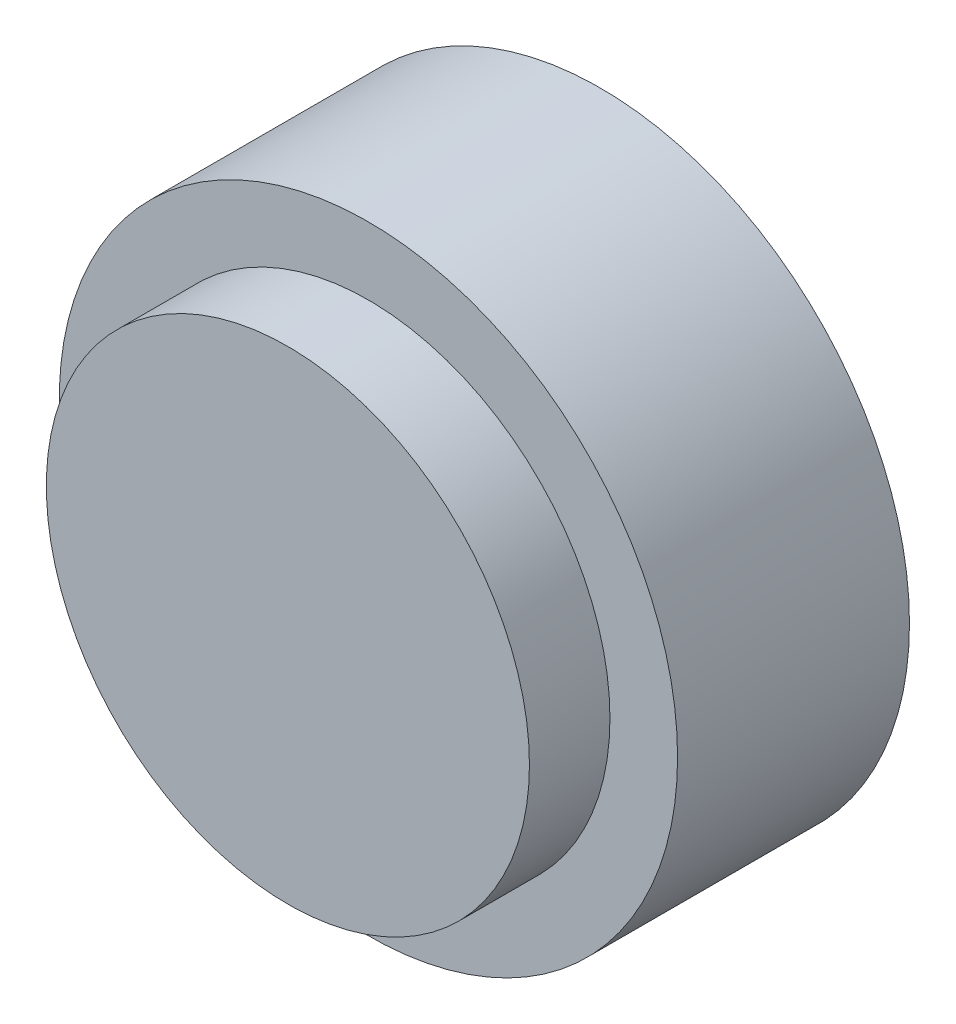
SolidWorks part; units mm, degrees
ref_plane "Front Plane" through (0, 0, 0) normal (0, 0, 1) x (1, 0, 0)
ref_plane "Top Plane" through (0, 0, 0) normal (0, 1, 0) x (1, 0, 0)
ref_plane "Right Plane" through (0, 0, 0) normal (1, 0, 0) x (0, 0, -1)
sketch "Sketch1" plane through (0, 0, 0) normal (0, 0, 1) x (1, 0, 0)
  circle A0 centre (0, 0) radius 48
  circle A1 centre (0, 0) radius 37.5
  circle A2 centre (0, 0) radius 21
  dimension "D1" = 96
  dimension "D2" = 75
  dimension "D3" = 42
extrude "Boss-Extrude1" add sketch "Sketch1" along normal blind 12.5 contours A1 A2 | A2 region at (-36.4393, 0, 0) region at (0, 0, 0)
extrude "Boss-Extrude2" add sketch "Sketch1<3>" against normal blind 36 contours A0 A1 | A1 A2 region at (-46.6424, 0, 0) region at (-36.4393, 0, 0)
sketch "Sketch1<3>" plane through (0, 0, 0) normal (0, 0, 1) x (1, 0, 0) same geometry as "Sketch1"
ref_plane "Plane1" through (0, 0, -36) normal (0, 0, -1) x (-1, 0, 0)
sketch "Sketch2" plane through (0, 0, -36) normal (0, 0, -1) x (-1, 0, 0)
  line L0 (0, 0) -> (0, 52.4537) construction
  circle A0 centre (0, 42) radius 2
  circle A1 centre (29.6985, 29.6985) radius 2
  circle A2 centre (42, 0) radius 2
  circle A3 centre (29.6985, -29.6985) radius 2
  circle A4 centre (0, -42) radius 2
  circle A5 centre (-29.6985, -29.6985) radius 2
  circle A6 centre (-42, 0) radius 2
  circle A7 centre (-29.6985, 29.6985) radius 2
  point P3 (0, 42)
  point P22 (0, 0)
  dimension "D2" = 4
  dimension "D1" = 42
  dimension "D3" = 8
hole_wizard "M4 Tapped Hole1" positions "Sketch3" profile "Sketch4" tap size "M4" standard "ISO"
sketch "Sketch3" plane through (0, 0, -36) normal (0, 0, -1) x (-1, 0, 0)
  point P0 (0, 42)
  point P3 (29.6985, 29.6985)
  point P6 (42, 0)
  point P9 (29.6985, -29.6985)
  point P12 (0, -42)
  point P15 (-29.6985, -29.6985)
  point P18 (-42, 0)
  point P21 (-29.6985, 29.6985)
sketch "Sketch4" plane through (0, 42, -36) normal (1, 0, 0) x (0, 1, 0)
  line L0 (0, 0) -> (0, 6.5914)
  line L1 (0, 6.5914) -> (1.65, 5.6)
  line L2 (1.65, 5.6) -> (1.65, 0.375)
  line L3 (1.65, 0.375) -> (2.025, 0)
  line L5 (2.025, 0) -> (0, 0)
  line L6 (-1.65, 0.375) -> (-2.025, 0) construction
  line L10 (0, 6.5914) -> (-1.65, 5.6) construction
  line L11 (0, -6.35) -> (0, 107.95) construction
  dimension "Tap Drill Dia." = 3.3
  dimension "Tap Drill Depth" = 5.6
  dimension "Near C'Sink Dia." = 4.05
  dimension "Near C'Sink Angle" = 90
  dimension "Drill Angle" = 118
cosmetic thread "Hole Thread1"
cosmetic thread "Hole Thread2"
cosmetic thread "Hole Thread3"
cosmetic thread "Hole Thread4"
cosmetic thread "Hole Thread5"
cosmetic thread "Hole Thread6"
cosmetic thread "Hole Thread7"
cosmetic thread "Hole Thread8"
